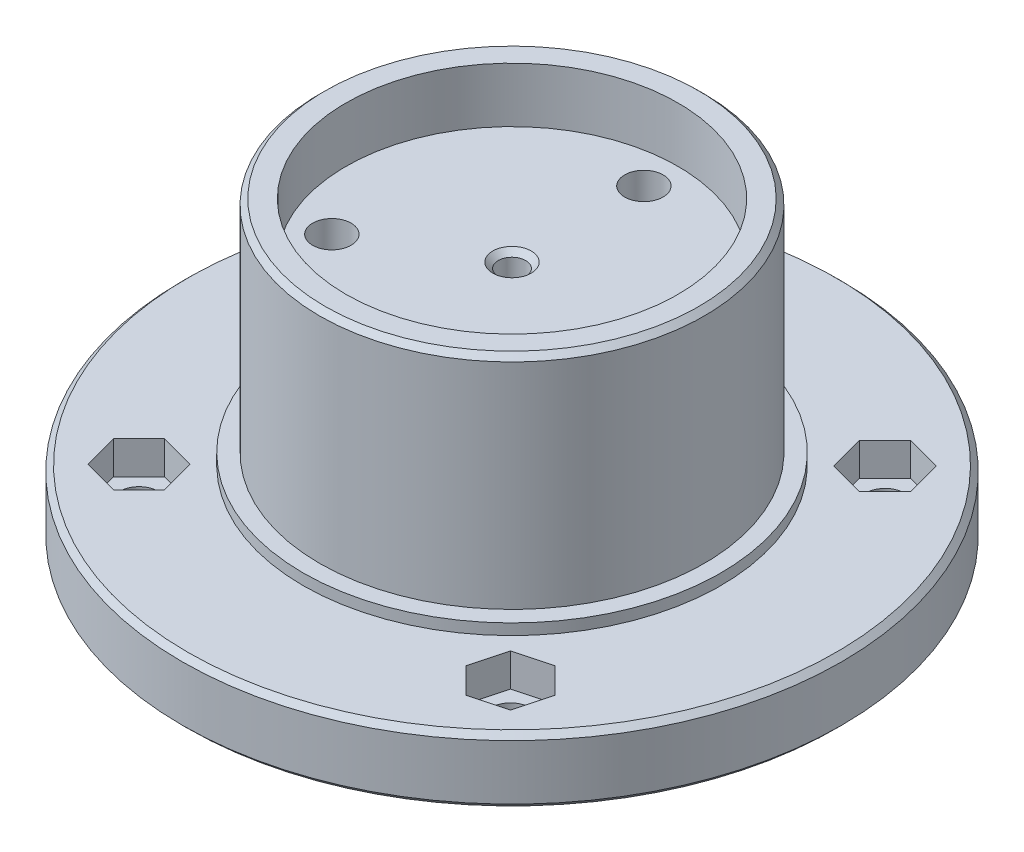
SolidWorks part; units mm, degrees
ref_plane "Front" through (0, 0, 0) normal (0, 0, 1) x (1, 0, 0)
ref_plane "Top" through (0, 0, 0) normal (0, 1, 0) x (1, 0, 0)
ref_plane "Right" through (0, 0, 0) normal (1, 0, 0) x (0, 0, -1)
sketch "Эскиз1" plane through (0, 0, 0) normal (0, 1, 0) x (1, 0, 0)
  circle A0 centre (0, 0) radius 30
extrude "Бобышка-Вытянуть1" add sketch "Эскиз1" along normal blind 6
sketch "Эскиз3" plane through (0, 0, 0) normal (0, 1, 0) x (1, 0, 0)
  circle A0 centre (0, 0) radius 19
extrude "Бобышка-Вытянуть2" add sketch "Эскиз3" along normal blind 1 from offset 6
sketch "Эскиз4" plane through (0, 0, 0) normal (0, 1, 0) x (1, 0, 0)
  circle A0 centre (0, 0) radius 17.5
extrude "Бобышка-Вытянуть3" add sketch "Эскиз4" along normal blind 20 from offset 7
sketch "Эскиз5" plane through (0, 27, 0) normal (0, 1, 0) x (1, 0, 0)
  circle A0 centre (0, 0) radius 15.1
  dimension "D1" = 30.2
extrude "Вырез-Вытянуть1" cut sketch "Эскиз5" against normal blind 5
sketch "Эскиз6" plane through (0, 0, 0) normal (0, 1, 0) x (1, 0, 0)
  circle A0 centre (0, 0) radius 12 construction
  circle A1 centre (0, 12) radius 1.75
extrude "Вырез-Вытянуть2" cut sketch "Эскиз6" along normal through all
pattern_circular "Круговой массив1" count 3 over 360 about axis through (0, 27, 0) along (0, -1, 0) of "Вырез-Вытянуть2"
sketch "Sketch1" plane through (0, 0, 0) normal (0, -1, 0) x (1, 0, 0)
  circle A0 centre (-10.3923, 6) radius 3.25
  circle A1 centre (10.3923, 6) radius 3.25
  circle A2 centre (0, -12) radius 3.25
  point P10 (0, 0)
  dimension "D1" = 3
extrude "Cut-Extrude1" cut sketch "Sketch1" against normal blind 14
sketch "Эскиз7" plane through (0, 0, 0) normal (0, -1, 0) x (1, 0, 0)
  circle A0 centre (0, 0) radius 1.25
extrude "Вырез-Вытянуть3" cut sketch "Эскиз7" against normal through all both and the other way through all
sketch "Эскиз8" plane through (0, 0, 0) normal (0, 1, 0) x (1, 0, 0)
  line L0 (0, 0) -> (17.0392, 16.9017) construction
  line L2 (14.7122, 14.5746) -> (17.8909, 13.7229)
  line L3 (17.8909, 13.7229) -> (20.218, 16.0499)
  line L4 (20.218, 16.0499) -> (19.3662, 19.2287)
  line L5 (19.3662, 19.2287) -> (16.1874, 20.0804)
  line L6 (16.1874, 20.0804) -> (13.8604, 17.7534)
  line L7 (13.8604, 17.7534) -> (14.7122, 14.5746)
  circle A0 centre (0, 0) radius 24 construction
  circle A1 centre (17.0392, 16.9017) radius 1.75
  circle A2 centre (17.0392, 16.9017) radius 2.85 construction
  dimension "D1" = 5.7
  dimension "D2" = 3.5
  dimension "D3" = 48
extrude "Вырез-Вытянуть4" cut sketch "Эскиз8" along normal through all contours A1
extrude "Вырез-Вытянуть5" cut sketch "Эскиз8<3>" along normal blind 10 from offset 3 contours L5 L6 L7 L2 L3 L4
sketch "Эскиз8<3>" plane through (0, 0, 0) normal (0, 1, 0) x (1, 0, 0) same geometry as "Эскиз8"
pattern_circular "Круговой массив2" count 4 over 360 about axis through (0, 6, 0) along (0, -1, 0) of "Вырез-Вытянуть5", "Вырез-Вытянуть4"
chamfer "Chamfer2" distance 0.5 angle 45 2 edges at (0, 0, 30) (0, 6, 30)
chamfer "Chamfer1" distance 0.5 angle 45 3 edges at (0, 27, 17.5) (0, 0, 1.25) (0, 22, 1.25)
